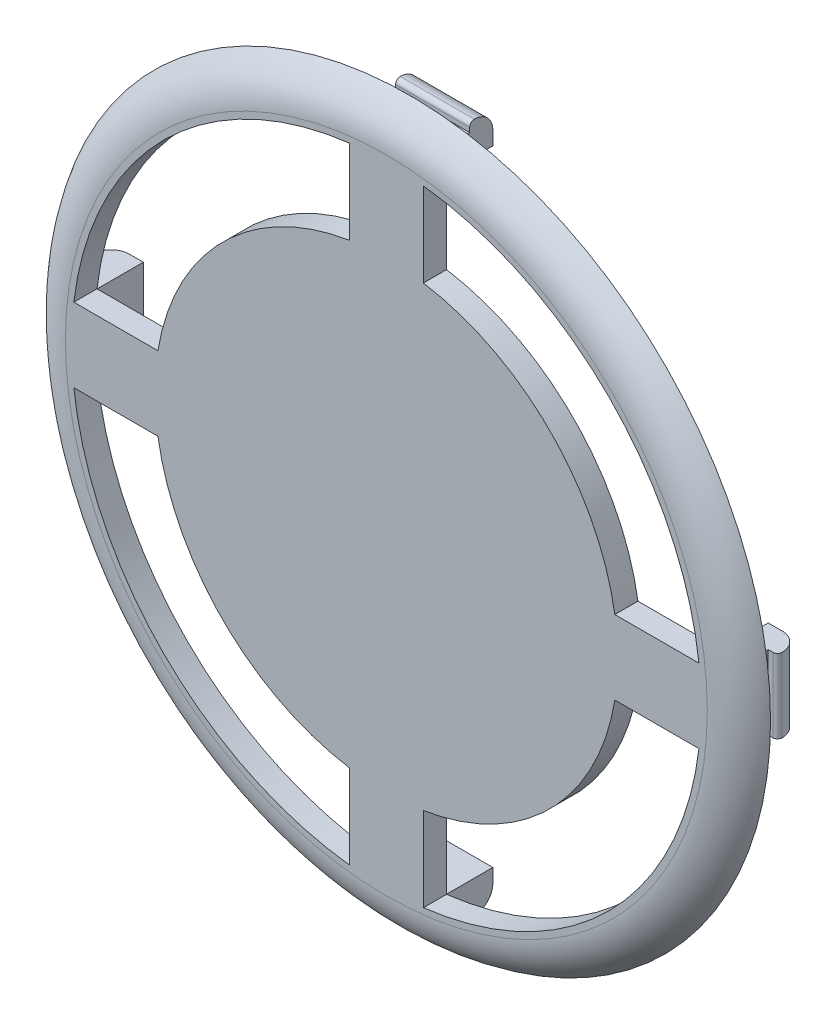
SolidWorks part; units mm, degrees
ref_plane "Front" through (0, 0, 0) normal (0, 0, 1) x (1, 0, 0)
ref_plane "Top" through (0, 0, 0) normal (0, 1, 0) x (1, 0, 0)
ref_plane "Right" through (0, 0, 0) normal (1, 0, 0) x (0, 0, -1)
sketch "ｽｹｯﾁ1" plane through (0, 0, 0) normal (0, 0, 1) x (1, 0, 0)
  circle A0 centre (0, 0) radius 39
  dimension "D1" = 78
extrude "ﾎﾞｽ - 押し出し1" add sketch "ｽｹｯﾁ1" along normal blind 2.5
fillet "ﾌｨﾚｯﾄ1" radius 5 1 edges at (39, 0, 2.5)
sketch "ｽｹｯﾁ2" plane through (0, 0, 0) normal (0, 0, -1) x (-1, 0, 0)
  line L0 (0, 0) -> (0, 42.9418) construction
  line L1 (0, 50) -> (0, -50) construction
  line L3 (-4, 36.25) -> (4, 36.25)
  line L4 (-4, 36.25) -> (-4, 33.75)
  line L5 (-4, 33.75) -> (4, 33.75)
  line L6 (4, 36.25) -> (4, 33.75)
  line L7 (-4, 36.25) -> (4, 33.75) construction
  line L8 (-4, 33.75) -> (4, 36.25) construction
  circle A0 centre (0, 0) radius 39 construction
  point P5 (0, 35)
  point P10 (0, 39)
  dimension "D1" = 8
  dimension "D2" = 2.5
  dimension "D3" = 2.75
  dimension "D4" = 36.47
extrude "ﾎﾞｽ - 押し出し2" add sketch "ｽｹｯﾁ2" along normal blind 5
sketch "ｽｹｯﾁ3" plane through (0, 36.25, 0) normal (0, 1, 0) x (1, 0, 0)
  line L0 (-4, 5) -> (-4, 0) construction
  line L1 (4, 5) -> (-4, 5)
  line L2 (4, 5) -> (4, 2.5)
  line L3 (4, 2.5) -> (-4, 2.5)
  line L4 (-4, 5) -> (-4, 2.5)
  line L7 (-4, 0) -> (4, 0) construction
  dimension "D1" = 2.5
extrude "ﾎﾞｽ - 押し出し3" add sketch "ｽｹｯﾁ3" along normal blind 1
sketch "ｽｹｯﾁ6" plane through (0, 0, 0) normal (0, 1, 0) x (1, 0, 0)
  line L0 (0, 0) -> (0, 26.6155) construction
fillet "ﾌｨﾚｯﾄ4" radius 0.5 1 edges at (0, 37.25, -2.5)
fillet "ﾌｨﾚｯﾄ5" radius 2 1 edges at (0, 37.25, -5)
pattern_circular "円形ﾊﾟﾀｰﾝ7" count 4 over 360 about axis through (0, 0, 0) along (0, 0, -1) of "ﾎﾞｽ - 押し出し2", "ﾎﾞｽ - 押し出し3", "ﾌｨﾚｯﾄ4", "ﾌｨﾚｯﾄ5" reverse direction yes
sketch "ｽｹｯﾁ7" plane through (0, 0, 0) normal (0, 0, -1) x (-1, 0, 0)
  line L0 (0, 0) -> (0, 40.8738) construction
  line L1 (0, 0) -> (49.9879, 0) construction
  line L2 (4, 33.75) -> (4, 36.25) construction
  line L3 (24.6779, 4) -> (33.7639, 4)
  line L4 (4, 24.6779) -> (4, 33.7639)
  line L12 (36.25, 4) -> (33.75, 4) construction
  arc A0 (4, 24.6779) -> (24.6779, 4) centre (0, 0) cw
  arc A1 (4, 33.7639) -> (33.7639, 4) centre (0, 0) cw
  dimension "D3" = 25
  dimension "D4" = 34
extrude "ｶｯﾄ - 押し出し1" cut sketch "ｽｹｯﾁ7" against normal through all
pattern_circular "円形ﾊﾟﾀｰﾝ8" count 4 over 360 about axis through (0, 0, 0) along (0, 0, -1) of "ｶｯﾄ - 押し出し1" reverse direction yes
